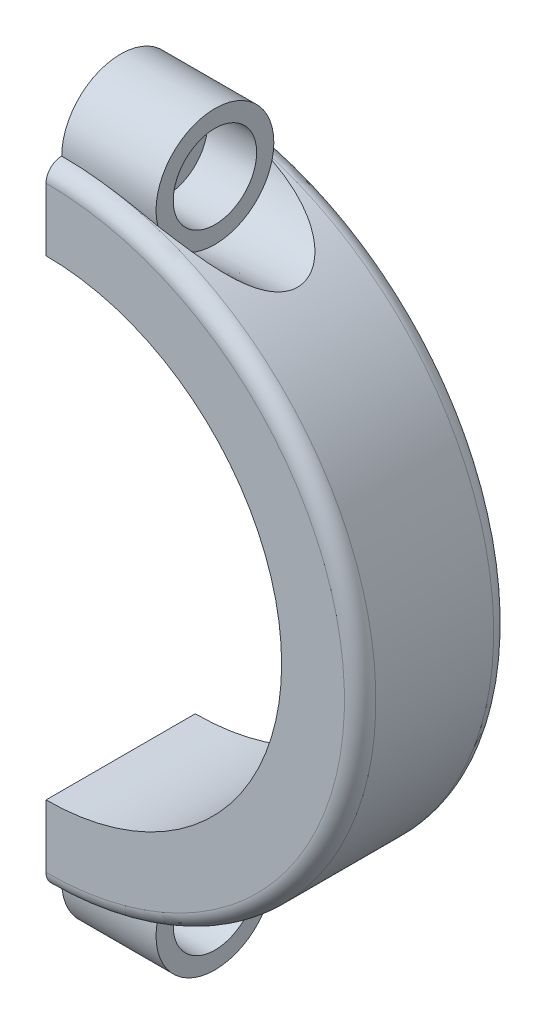
SolidWorks part; units mm, degrees
ref_plane "Front Plane" through (0, 0, 0) normal (0, 0, 1) x (1, 0, 0)
ref_plane "Top Plane" through (0, 0, 0) normal (0, 1, 0) x (1, 0, 0)
ref_plane "Right Plane" through (0, 0, 0) normal (1, 0, 0) x (0, 0, -1)
sketch "Sketch1" plane through (0, 0, 0) normal (0, 0, 1) x (1, 0, 0)
  line L0 (0, 50.8) -> (0, 38.1)
  line L1 (0, -38.1) -> (0, -50.8)
  arc A0 (0, -50.8) -> (0, 50.8) centre (0, 0) ccw
  arc A1 (0, -38.1) -> (0, 38.1) centre (0, 0) ccw
  dimension "D1" = 76.2
  dimension "D2" = 12.7
extrude "Boss-Extrude1" add sketch "Sketch1" along normal blind 24.13
sketch "Sketch2" plane through (0, 0, 0) normal (-1, 0, 0) x (0, 0, 1)
  line L0 (24.13, -50.8) -> (0, -50.8) construction
  circle A0 centre (12.065, -50.8) radius 9.525
  dimension "D1" = 19.05
extrude "Boss-Extrude2" add sketch "Sketch2" against normal blind 15.25
extrude "Cut-Extrude1" cut sketch "Sketch2<3>" against normal blind 15.25 draft 3 from offset 15.25 offset against normal yes
sketch "Sketch2<3>" plane through (0, 0, 0) normal (-1, 0, 0) x (0, 0, 1) same geometry as "Sketch2"
hole_wizard "CBORE for 5/16 Socket Head Cap Screw2" positions "3DSketch2" profile "Sketch4" counterbore size "5/16" standard "ANSI Inch" end condition through all
sketch3d "3DSketch2"
  line L0 (15.25, -50.8, 12.065) -> (0, -50.8, 12.065) construction
  point P0 (15.25, -50.8, 12.065)
sketch "Sketch4" plane through (15.25, -50.8, 12.065) normal (0, 1, 0) x (0, 0, -1)
  line L0 (0, 0) -> (0, 15.25)
  line L1 (0, 15.25) -> (4.2164, 15.25)
  line L3 (4.2164, 15.25) -> (4.2164, 7.9375)
  line L4 (4.2164, 7.9375) -> (6.7475, 7.9375)
  line L5 (6.7475, 7.9375) -> (6.7475, 0)
  line L7 (6.7475, 0) -> (0, 0)
  line L11 (0, -6.35) -> (0, 107.95) construction
  dimension "Thru Hole Dia." = 8.4328
  dimension "Thru Hole Depth" = 15.25
  dimension "C'Bore Dia." = 13.495
  dimension "C'Bore Depth" = 7.9375
mirror "Mirror1" about plane through (0, 0, 0) normal (0, 1, 0) of "Cut-Extrude1", "Boss-Extrude2", "CBORE for 5/16 Socket Head Cap Screw2"
fillet "Fillet1" radius 2.54 2 edges at (50.8, 0, 24.13) (50.8, 0, 0)
